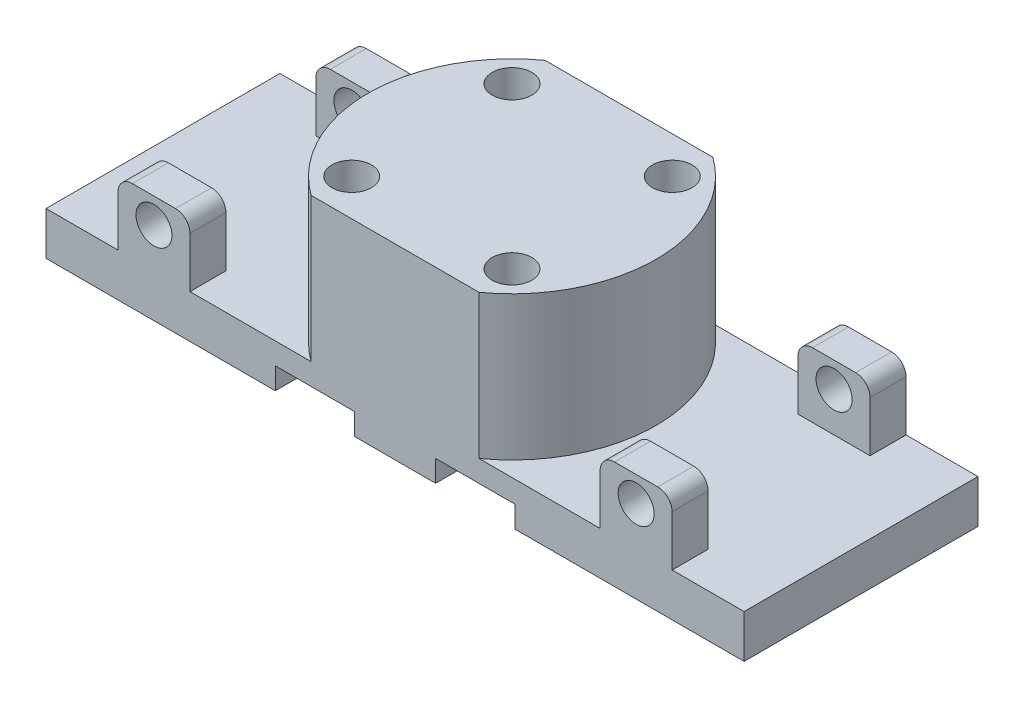
SolidWorks part; units mm, degrees
ref_plane "Front Plane" through (0, 0, 0) normal (0, 0, 1) x (1, 0, 0)
ref_plane "Top Plane" through (0, 0, 0) normal (0, 1, 0) x (1, 0, 0)
ref_plane "Right Plane" through (0, 0, 0) normal (1, 0, 0) x (0, 0, -1)
sketch "Sketch1" plane through (0, 0, 0) normal (0, 1, 0) x (1, 0, 0)
  line L1 (0, 0) -> (97, 0)
  line L2 (0, 0) -> (0, 32.5)
  line L3 (0, 32.5) -> (97, 32.5)
  line L4 (97, 0) -> (97, 32.5)
  point P5 (58.5, 26.25)
  dimension "D1" = 97
  dimension "D2" = 32.5
extrude "Boss-Extrude1" add sketch "Sketch1" along normal blind 6 contours L3 L4 L1 L2
sketch "Sketch5" plane through (0, 6, 0) normal (0, 1, 0) x (1, 0, 0)
  line L0 (48.5, 32.5) -> (48.5, 0) construction
  line L1 (0, 32.5) -> (97, 32.5) construction
  line L2 (0, 0) -> (97, 0) construction
  circle A0 centre (48.5, 16.25) radius 20
  point P3 (0, 0)
  dimension "D1" = 40
extrude "Boss-Extrude5" add sketch "Sketch5" along normal blind 20
sketch "Sketch6" plane through (0, 26, 0) normal (0, 1, 0) x (1, 0, 0)
  line L0 (48.5, 16.25) -> (48.5, -3.75)
  circle A0 centre (48.5, 16.25) radius 20 construction
sketch "Sketch7" plane through (0, 26, 0) normal (0, 1, 0) x (1, 0, 0)
  arc A15 (61.7369, 5.1131) -> (57.5369, 5.1131) centre (59.6369, 5.1131) ccw
  arc A16 (57.5369, 5.1131) -> (61.7369, 5.1131) centre (59.6369, 5.1131) ccw
  arc A17 (51, 0.5) -> (46, 0.5) centre (48.5, 0.5) ccw
  arc A18 (46, 0.5) -> (51, 0.5) centre (48.5, 0.5) ccw
  arc A19 (39.4631, 5.1131) -> (35.2631, 5.1131) centre (37.3631, 5.1131) ccw
  arc A20 (35.2631, 5.1131) -> (39.4631, 5.1131) centre (37.3631, 5.1131) ccw
  arc A21 (39.4631, 27.3869) -> (35.2631, 27.3869) centre (37.3631, 27.3869) ccw
  arc A22 (35.2631, 27.3869) -> (39.4631, 27.3869) centre (37.3631, 27.3869) ccw
  arc A23 (61.7369, 27.3869) -> (57.5369, 27.3869) centre (59.6369, 27.3869) ccw
  arc A24 (57.5369, 27.3869) -> (61.7369, 27.3869) centre (59.6369, 27.3869) ccw
  point P3 (0, 0)
  point P7 (0, 0)
  point P9 (0, 0)
  point P15 (0, 0)
  point P19 (79.6369, 37.3869)
sketch "Sketch10" plane through (0, 0, 0) normal (0, -1, 0) x (1, 0, 0)
  point P15 (37.3631, -5.1131)
  point P18 (59.6369, -5.1131)
  point P21 (59.6369, -27.3869)
  point P24 (37.3631, -27.3869)
  point P28 (0, 0)
  point P29 (0, 0)
  point P30 (0, 0)
  point P31 (0, 0)
hole_wizard "CBORE for M5 Hex Socket Head Cap Screw1" positions "Sketch10" profile "Sketch12" counterbore size "M5" standard "DIN" end condition through all
sketch "Sketch12" plane through (37.3631, 0, -5.1131) normal (1, 0, 0) x (0, 0, -1)
  line L0 (0, 0) -> (0, 26)
  line L1 (0, 26) -> (2.75, 26)
  line L3 (2.75, 26) -> (2.75, 5.9)
  line L4 (2.75, 5.9) -> (5, 5.9)
  line L5 (5, 5.9) -> (5, 0)
  line L7 (5, 0) -> (0, 0)
  line L11 (0, -6.35) -> (0, 107.95) construction
  dimension "Thru Hole Dia." = 5.5
  dimension "Thru Hole Depth" = 26
  dimension "C'Bore Dia." = 10
  dimension "C'Bore Depth" = 5.9
sketch "Sketch15" plane through (0, 6, 0) normal (0, 1, 0) x (1, 0, 0)
  line L0 (80.6754, 42.9481) -> (111.5983, 42.9481) construction
  line L1 (80.6754, 45.0519) -> (111.5983, 45.0519)
  line L2 (80.6754, 40.8443) -> (111.5983, 40.8443)
  arc A0 (80.6754, 45.0519) -> (80.6754, 40.8443) centre (80.6754, 42.9481) ccw
  arc A1 (111.5983, 40.8443) -> (111.5983, 45.0519) centre (111.5983, 42.9481) ccw
  point P2 (96.1368, 42.9481)
extrude "Cut-Extrude2" [suppressed] cut sketch "Sketch15" against normal blind 10
chamfer "Chamfer1" [suppressed] distance 1 angle 45
sketch "Sketch16" plane through (0, 0, 0) normal (0, 0, 1) x (1, 0, 0)
  line L0 (87, 6) -> (77, 6)
  line L1 (87, 6) -> (87, 13)
  line L2 (77, 6) -> (77, 13)
  line L3 (10, 6) -> (10, 13)
  line L4 (12, 15) -> (18, 15)
  line L5 (20, 6) -> (20, 13)
  line L6 (0, 6) -> (36.8408, 6) construction
  line L7 (10, 6) -> (20, 6)
  line L8 (85, 15) -> (79, 15)
  line L9 (48.5, 0) -> (48.5, 6) construction
  line L10 (0, 0) -> (97, 0) construction
  line L11 (68.5, 6) -> (28.5, 6) construction
  arc A0 (87, 13) -> (85, 15) centre (85, 13) ccw
  circle A1 centre (15, 11.5) radius 2.5
  arc A2 (18, 15) -> (20, 13) centre (18, 13) cw
  arc A3 (10, 13) -> (12, 15) centre (12, 13) cw
  arc A4 (79, 15) -> (77, 13) centre (79, 13) ccw
  circle A5 centre (82, 11.5) radius 2.5
  point P19 (10, 6)
  point P20 (0, 0)
  dimension "D1" = 2
  dimension "D7" = 2
  dimension "D8" = 5
  dimension "D2" = 5
  dimension "D3" = 10
  dimension "D4" = 9
  dimension "D5" = 10
  dimension "D6" = 3.5
extrude "Boss-Extrude6" add sketch "Sketch16" against normal blind 5
extrude "Boss-Extrude7" add sketch "Sketch16<2>" along normal blind 5 from surface starting at face at (48.5, 4, -32.5)
sketch "Sketch16<2>" plane through (0, 0, 0) normal (0, 0, 1) x (1, 0, 0) same geometry as "Sketch16"
sketch "Sketch17" plane through (0, 0, 0) normal (0, -1, 0) x (1, 0, 0)
  line L0 (31.8631, -27.3869) -> (31.8631, -32.5)
  line L1 (0, -32.5) -> (97, -32.5) construction
  line L2 (42.8631, -27.3869) -> (42.8631, -32.5)
  line L3 (31.8631, -32.5) -> (42.8631, -32.5)
  line L4 (68.5, -16.25) -> (28.5, -16.25) construction
  line L6 (48.5, -32.5) -> (48.5, 0) construction
  line L7 (65.1369, -27.3869) -> (65.1369, -32.5)
  line L8 (65.1369, -32.5) -> (54.1369, -32.5)
  line L9 (54.1369, -27.3869) -> (54.1369, -32.5)
  line L10 (54.1369, -5.1131) -> (54.1369, 0)
  line L11 (65.1369, 0) -> (54.1369, 0)
  line L12 (65.1369, -5.1131) -> (65.1369, 0)
  line L13 (31.8631, -5.1131) -> (31.8631, 0)
  line L14 (31.8631, 0) -> (42.8631, 0)
  line L15 (42.8631, -5.1131) -> (42.8631, 0)
  arc A0 (42.8631, -27.3869) -> (31.8631, -27.3869) centre (37.3631, -27.3869) ccw
  circle A4 centre (48.5, -16.25) radius 20 construction
  arc A5 (54.1369, -27.3869) -> (65.1369, -27.3869) centre (59.6369, -27.3869) cw
  arc A6 (54.1369, -5.1131) -> (65.1369, -5.1131) centre (59.6369, -5.1131) ccw
  arc A7 (42.8631, -5.1131) -> (31.8631, -5.1131) centre (37.3631, -5.1131) cw
  point P21 (48.5, -16.25)
  point P28 (48.5, -16.25)
  circle M2 centre (37.3631, -5.1131) radius 5
  circle M3 centre (59.6369, -5.1131) radius 5
  circle M4 centre (59.6369, -27.3869) radius 5
  circle M5 centre (37.3631, -27.3869) radius 5
  line M7 (0, -32.5) -> (97, -32.5)
  line M9 (97, 0) -> (0, 0)
  dimension "D4" = 11
extrude "Cut-Extrude3" cut sketch "Sketch17" against normal blind 3 contours L2 A0 L0 M7 M5 | A5 L9 L7 M7 M4 | L10 A6 L12 M9 M3 | A7 L15 L13 M9 M2 | M5 | M4 | M3 | M2 region at (37.3631, 0, -22.0398) region at (54.2898, 0, -29.9435) region at (42.7102, 0, -2.5565) region at (54.2898, 0, -2.5565) region at (37.3631, 0, -5.1131) region at (59.6369, 0, -5.1131) region at (59.6369, 0, -27.3869) region at (37.3631, 0, -27.3869)
sketch "Sketch18" plane through (0, 5.9, 0) normal (0, -1, 0) x (1, 0, 0)
  circle A0 centre (59.6369, -27.3869) radius 2.75 construction
  circle A1 centre (37.3631, -27.3869) radius 5
  circle A2 centre (37.3631, -27.3869) radius 5
  circle A3 centre (37.3631, -5.1131) radius 5
  circle A4 centre (37.3631, -5.1131) radius 5
  circle A5 centre (59.6369, -5.1131) radius 5
  circle A6 centre (59.6369, -5.1131) radius 5
  circle A7 centre (59.6369, -27.3869) radius 5
  circle A8 centre (59.6369, -27.3869) radius 5
  circle A9 centre (37.3631, -27.3869) radius 2.75 construction
  circle A10 centre (59.6369, -5.1131) radius 2.75 construction
  circle A11 centre (37.3631, -5.1131) radius 2.75 construction
  circle A12 centre (59.6369, -27.3869) radius 2.75
  circle A13 centre (37.3631, -27.3869) radius 2.75
  circle A14 centre (59.6369, -5.1131) radius 2.75
  circle A15 centre (37.3631, -5.1131) radius 2.75
  dimension "D1" = 0
  dimension "D2" = 0
  dimension "D3" = 0
  dimension "D4" = 0
extrude "Boss-Extrude8" add sketch "Sketch18" along normal up to surface (2.9 mm away) up to face at (37.3631, 3, -3.9315)
sketch "Sketch19" plane through (0, 6, 0) normal (0, -1, 0) x (1, 0, 0)
  line L1 (36.8408, 0) -> (60.1592, 0)
  line L2 (36.8408, 0) -> (60.1592, 0)
  line L3 (60.1592, -32.5) -> (36.8408, -32.5)
  line L4 (60.1592, -32.5) -> (36.8408, -32.5)
  arc A1 (60.1592, 0) -> (36.8408, 0) centre (48.5, -16.25) ccw
  arc A2 (60.1592, 0) -> (36.8408, 0) centre (48.5, -16.25) ccw
  arc A3 (36.8408, -32.5) -> (60.1592, -32.5) centre (48.5, -16.25) ccw
  arc A4 (36.8408, -32.5) -> (60.1592, -32.5) centre (48.5, -16.25) ccw
  arc M5 (60.1592, 0) -> (36.8408, 0) centre (48.5, -16.25) ccw
  line M6 (36.8408, 0) -> (60.1592, 0)
  dimension "D1" = 0
  dimension "D2" = 0
extrude "Cut-Extrude4" cut sketch "Sketch19" against normal up to surface (20 mm away) contours M6 M5 | L4 A4 region at (48.5, 6, 1.5127) region at (48.5, 6, -34.0127) up to face at (37.3631, 26, -7.8631)
